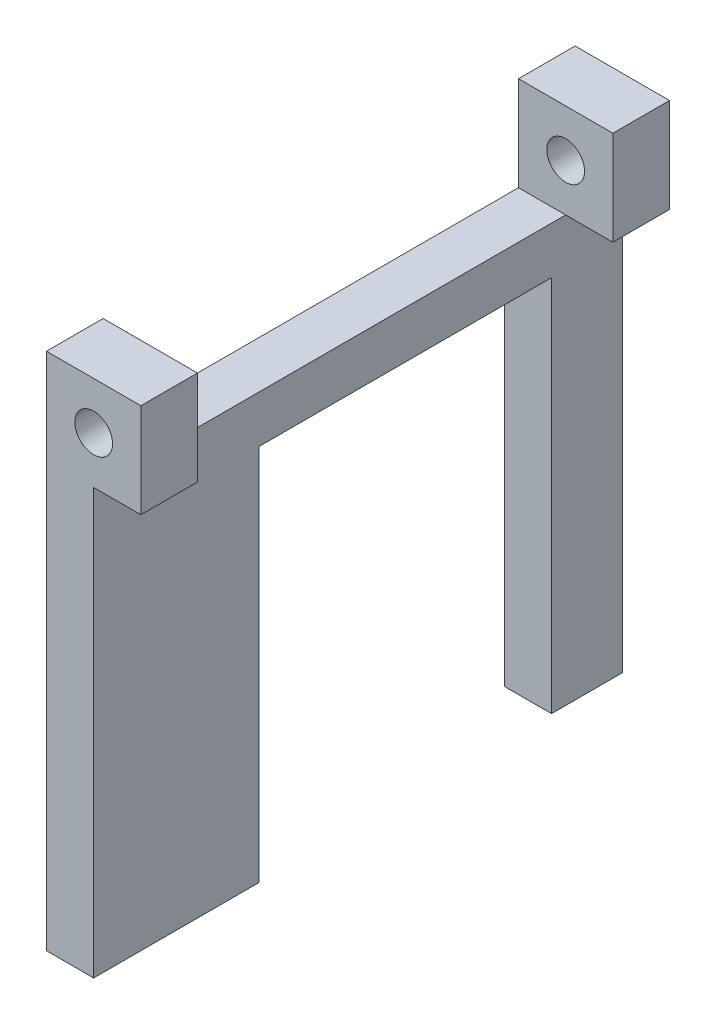
SolidWorks part; units mm, degrees
material "1060 合金"
ref_plane "前视基准面" through (0, 0, 0) normal (0, 0, 1) x (1, 0, 0)
ref_plane "上视基准面" through (0, 0, 0) normal (0, 1, 0) x (1, 0, 0)
ref_plane "右视基准面" through (0, 0, 0) normal (1, 0, 0) x (0, 0, -1)
sketch "草图3" plane through (0, 0, 0) normal (1, 0, 0) x (0, 0, -1)
  line L0 (0, 0) -> (0, 125.5508) construction
  line L1 (-85.8608, 0) -> (0, 0) construction
  line L2 (41, 0) -> (56, 0)
  line L3 (-56, 90) -> (56, 90)
  line L4 (-56, 90) -> (-56, 0)
  line L5 (-56, 0) -> (-21, 0)
  line L6 (56, 90) -> (56, 0)
  line L9 (41, 80) -> (-21, 80)
  line L10 (41, 80) -> (41, 0)
  line L12 (-21, 80) -> (-21, 0)
  line L15 (0, 0) -> (85.183, 0) construction
  dimension "D1" = 90
  dimension "D2" = 15
  dimension "D3" = 80
  dimension "D4" = 62
  dimension "D5" = 35
extrude "凸台-拉伸2" add sketch "草图3" along normal mid plane 10
sketch "草图5" plane through (0, 0, 56) normal (0, 0, 1) x (1, 0, 0)
  line L0 (-5, 100) -> (15, 100) construction
  line L1 (-5, 90) -> (15, 90)
  line L2 (-5, 90) -> (-5, 110)
  line L3 (-5, 110) -> (15, 110)
  line L4 (15, 90) -> (15, 110)
  line L7 (15, 100) -> (5, 110) construction
  line L8 (5, 110) -> (5, 90) construction
  line L10 (5, 90) -> (-5, 90) construction
  line L11 (-5, 90) -> (-5, 0) construction
  circle A0 centre (5, 100) radius 4
  dimension "D3" = 8
  dimension "D1" = 20
  dimension "D2" = 20
extrude "凸台-拉伸3" add sketch "草图5" against normal blind 12
mirror "镜向1" about plane through (0, 0, 0) normal (0, 0, 1) of "凸台-拉伸3"
move or copy body "实体-移动/复制1" [suppressed] bodies to move or copy 104
